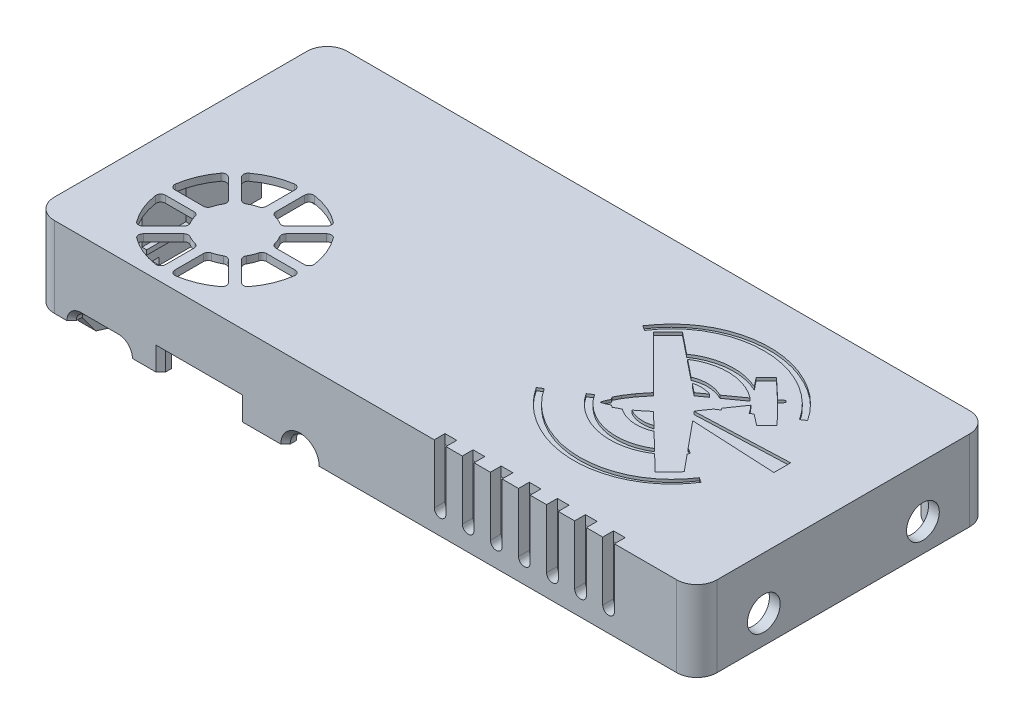
SolidWorks part; units mm, degrees
ref_plane "Front Plane" through (0, 0, 0) normal (0, 0, 1) x (1, 0, 0)
ref_plane "Top Plane" through (0, 0, 0) normal (0, 1, 0) x (1, 0, 0)
ref_plane "Right Plane" through (0, 0, 0) normal (1, 0, 0) x (0, 0, -1)
sketch "Sketch1" plane through (0, 0, 0) normal (0, 1, 0) x (1, 0, 0)
  line L0 (-71.5618, 3.106) -> (63.4382, 3.106) construction
  line L1 (-71.5618, 31.106) -> (63.4382, 31.106)
  line L2 (-71.5618, 31.106) -> (-71.5618, -24.894)
  line L3 (-71.5618, -24.894) -> (63.4382, -24.894)
  line L4 (63.4382, 31.106) -> (63.4382, -24.894)
  line L5 (-60.6618, -24.894) -> (-60.6618, -31.6828) construction
  line L6 (-68.0618, 27.606) -> (-10.0618, 27.606)
  line L7 (-68.0618, 27.606) -> (-68.0618, -21.394)
  line L8 (-68.0618, -21.394) -> (-10.0618, -21.394)
  line L9 (-10.0618, 27.606) -> (-10.0618, -21.394)
  line L10 (-39.5618, -24.894) -> (-39.5618, -31.6828) construction
  line L11 (-18.0618, -24.894) -> (-18.0618, -31.6828) construction
  line L12 (-65.4118, -26.5648) -> (-55.9118, -26.5648) construction
  line L13 (-48.0618, -26.5648) -> (-31.0618, -26.5648) construction
  line L14 (-22.0618, -26.5648) -> (-14.0618, -26.5648) construction
  line L15 (-72.5618, 9.606) -> (-72.5618, -3.394) construction
  line L16 (-71.5618, 3.106) -> (-72.5618, 3.106) construction
  line L17 (-60.6618, -24.894) -> (-60.6618, 40.2849) construction
  dimension "D1" = 135
  dimension "D2" = 56
  dimension "D3" = 49
  dimension "D4" = 58
  dimension "D5" = 3.5
  dimension "D6" = 3.5
  dimension "D7" = 10.9
  dimension "D8" = 32
  dimension "D9" = 53.5
  dimension "D10" = 2
  dimension "D11" = 13
  dimension "D12" = 9.5
  dimension "D13" = 17
  dimension "D14" = 8
sketch "Sketch3" plane through (0, 0, 0) normal (0, 1, 0) x (1, 0, 0)
  line L2 (-72.5618, -25.894) -> (64.4382, -25.894) construction
  line L3 (66.7382, -28.194) -> (66.7382, 34.406) construction
  line L4 (66.7382, 34.406) -> (-74.8618, 34.406)
  line L5 (-74.8618, 34.406) -> (-74.8618, -28.194)
  line L6 (-74.8618, -28.194) -> (66.7382, -28.194)
  line L8 (64.4382, 32.106) -> (-72.5618, 32.106)
  line L9 (64.4382, -25.894) -> (64.4382, 32.106)
  line L10 (-72.5618, -25.894) -> (64.4382, -25.894)
  line L11 (-72.5618, 32.106) -> (-72.5618, -25.894)
  line L12 (64.4382, 32.106) -> (-72.5618, 32.106)
  line L13 (64.4382, -25.894) -> (64.4382, 32.106)
  line L14 (-72.5618, -25.894) -> (64.4382, -25.894)
  line L15 (-72.5618, 32.106) -> (-72.5618, -25.894)
  line L16 (-4.0618, 3.106) -> (-4.0618, 34.406) construction
  line L17 (-71.5618, 3.106) -> (63.4382, 3.106) construction
  line L18 (64.4382, -25.894) -> (64.4382, 32.106) construction
  line L20 (-74.8618, 3.106) -> (52.7382, 3.106) construction
  line L22 (-74.8618, -28.194) -> (66.7382, -28.194) construction
  line L23 (66.7382, -28.194) -> (66.7382, 34.406)
  dimension "D1" = 1
  dimension "D2" = 2.3
extrude "Boss-Extrude1" add sketch "Sketch3" along normal blind 17.2
sketch "Sketch5" plane through (0, 0, 0) normal (0, 1, 0) x (1, 0, 0)
  line L1 (-72.5618, 32.106) -> (64.4382, 32.106)
  line L2 (-72.5618, 32.106) -> (-72.5618, -25.894)
  line L3 (-72.5618, -25.894) -> (64.4382, -25.894)
  line L4 (64.4382, 32.106) -> (64.4382, -25.894)
sketch "Sketch11" plane through (0, 0, 28.194) normal (0, 0, 1) x (1, 0, 0)
  line L0 (-74.8618, 17.2) -> (-74.8618, 0) construction
  line L2 (-66.8618, 0) -> (-54.8618, 0)
  line L3 (-66.8618, 0) -> (-66.8618, 2)
  line L4 (-66.8618, 2) -> (-54.8618, 2)
  line L5 (-54.8618, 0) -> (-54.8618, 2)
  line L9 (-47.8118, 4) -> (-31.3118, 4)
  line L10 (-47.8118, 4) -> (-47.8118, 0)
  line L11 (-47.8118, 0) -> (-31.3118, 0)
  line L12 (-31.3118, 4) -> (-31.3118, 0)
  line L14 (-39.5618, 0) -> (-39.528, 10.3) construction
  line L15 (-48.0618, 0) -> (-31.0618, 0) construction
  line L16 (-18.0618, 0) -> (-18.0618, 10.3) construction
  line L17 (-22.0618, 0) -> (-14.0618, 0) construction
  circle A0 centre (-18.0618, 0) radius 3.1
  dimension "D5" = 6.2
  dimension "D1" = 4
  dimension "D2" = 2
  dimension "D3" = 12
  dimension "D4" = 16.5
  dimension "D7" = 8
extrude "Cut-Extrude1" cut sketch "Sketch11" against normal up to next
sketch "Sketch14" plane through (0, 0, 0) normal (0, -1, 0) x (1, 0, 0)
  line L1 (-74.8618, 11.894) -> (-72.5618, 11.894)
  line L2 (-74.8618, 11.894) -> (-74.8618, -18.106)
  line L3 (-74.8618, -18.106) -> (-72.5618, -18.106)
  line L4 (-72.5618, 11.894) -> (-72.5618, -18.106)
  dimension "D1" = 30
extrude "Boss-Extrude6" add sketch "Sketch14" along normal blind 2.8
sketch "Sketch15" plane through (-74.8618, 0, 0) normal (-1, 0, 0) x (0, 0, 1)
  line L0 (11.894, -2.8) -> (-18.106, -2.8) construction
  line L1 (-9.7403, -2.8) -> (3.7597, -2.8)
  line L2 (-9.7403, -2.8) -> (-9.7403, -1.8)
  line L3 (-9.7403, -1.8) -> (3.7597, -1.8)
  line L4 (3.7597, -2.8) -> (3.7597, -1.8)
sketch "Sketch94" plane through (0, -2.8, 0) normal (0, -1, 0) x (1, 0, 0)
  line L0 (-74.8618, -9.7403) -> (-74.8618, 3.7597) construction
  line L1 (-72.5618, 3.7671) -> (-74.8618, 3.7671)
  line L2 (-72.5618, 3.7671) -> (-72.5618, -9.7403)
  line L3 (-72.5618, -9.7403) -> (-74.8618, -9.7403)
  line L4 (-74.8618, 3.7671) -> (-74.8618, -9.7403)
  line L5 (-74.8618, -30.106) -> (-74.8618, -9.7329) construction
extrude "Boss-Extrude11" add sketch "Sketch94" along normal blind 1.5
sketch "Sketch35" plane through (0, 17.2, 0) normal (0, 1, 0) x (1, 0, 0)
  line L1 (-72.5618, 32.106) -> (64.4382, 32.106)
  line L2 (-72.5618, 32.106) -> (-72.5618, -25.894)
  line L3 (-72.5618, -25.894) -> (64.4382, -25.894)
  line L4 (64.4382, 32.106) -> (64.4382, -25.894)
extrude "Boss-Extrude7" add sketch "Sketch35" against normal blind 2
sketch "Sketch36" plane through (0, 17.2, 0) normal (0, 1, 0) x (1, 0, 0)
  line L0 (24.1618, 0.3922) -> (23.0119, -0.3579)
  line L1 (34.6516, 0.4143) -> (35.8046, -0.3309)
  line L2 (24.1474, 7.2037) -> (22.9944, 7.949)
  line L3 (34.6373, 7.2258) -> (35.7871, 7.9759)
  line L4 (45.9489, -6.8877) -> (46.9923, -7.5622)
  line L5 (39.4174, -2.6661) -> (40.5245, -3.3816)
  line L6 (19.409, -2.7082) -> (18.305, -3.4284)
  line L7 (12.8953, -6.9573) -> (11.8548, -7.6361)
  line L8 (12.8501, 14.5058) -> (11.8067, 15.1802)
  line L9 (19.3816, 10.2841) -> (18.2746, 10.9997)
  line L10 (39.3901, 10.3263) -> (40.4941, 11.0465)
  line L11 (45.9037, 14.5754) -> (46.9443, 15.2542)
  line L12 (52.9704, 2.0329) -> (31.2725, 3.1101)
  line L13 (52.9704, 5.6235) -> (31.2725, 4.7515)
  line L14 (52.9704, 2.0329) -> (52.9704, 5.6235)
  line L15 (31.2725, 3.1101) -> (31.2725, 4.7515)
  arc A0 (46.9443, 15.2542) -> (11.8067, 15.1802) centre (29.3995, 3.809) ccw
  arc A1 (45.9037, 14.5754) -> (12.8501, 14.5058) centre (29.3995, 3.809) ccw
  arc A2 (34.6373, 7.2258) -> (24.1474, 7.2037) centre (29.3995, 3.809) ccw
  arc A3 (35.7871, 7.9759) -> (22.9944, 7.949) centre (29.3995, 3.809) ccw
  arc A4 (40.4941, 11.0465) -> (18.2746, 10.9997) centre (29.3995, 3.809) ccw
  arc A5 (39.3901, 10.3263) -> (19.3816, 10.2841) centre (29.3995, 3.809) ccw
  arc A6 (11.8548, -7.6361) -> (46.9923, -7.5622) centre (29.3995, 3.809) ccw
  arc A7 (12.8953, -6.9573) -> (45.9489, -6.8877) centre (29.3995, 3.809) ccw
  arc A8 (18.305, -3.4284) -> (40.5245, -3.3816) centre (29.3995, 3.809) ccw
  arc A9 (19.409, -2.7082) -> (39.4174, -2.6661) centre (29.3995, 3.809) ccw
  arc A10 (23.0119, -0.3579) -> (35.8046, -0.3309) centre (29.3995, 3.809) ccw
  arc A11 (24.1618, 0.3922) -> (34.6516, 0.4143) centre (29.3995, 3.809) ccw
extrude "Cut-Extrude4" cut sketch "Sketch36" against normal blind 0.6
sketch "Sketch37" plane through (0, 17.2, 0) normal (0, 1, 0) x (1, 0, 0)
  line L0 (28.805, 0.4761) -> (40.1826, -10.5566)
  line L1 (40.1826, -10.5566) -> (43.2384, -7.4053)
  line L2 (43.2384, -7.4053) -> (33.0944, 4.8995)
  line L3 (33.0944, 4.8995) -> (38.1664, 12.1985)
  line L4 (38.1664, 12.1985) -> (42.4176, 8.9024)
  line L5 (42.4176, 8.9024) -> (44.5689, 11.121)
  line L6 (44.5689, 11.121) -> (40.5449, 15.2662)
  line L7 (40.5449, 15.2662) -> (41.3442, 16.2971)
  line L8 (41.3442, 16.2971) -> (41.1146, 16.4751)
  line L9 (28.805, 0.4761) -> (26.7077, -1.2529)
  line L10 (26.7077, -1.2529) -> (24.9219, -2.47)
  line L11 (24.9219, -2.47) -> (23.6139, -3.1724)
  line L12 (23.6139, -3.1724) -> (23.1085, -2.8212)
  line L13 (23.1085, -2.8212) -> (22.3443, -3.2316)
  line L14 (22.3443, -3.2316) -> (21.6545, -3.4615)
  line L15 (21.6545, -3.4615) -> (21.4618, -3.4615)
  line L16 (41.1146, 16.4751) -> (21.4618, -3.4615) construction
  line L17 (21.459, -3.2688) -> (21.4618, -3.4615)
  line L18 (21.6791, -2.5758) -> (21.459, -3.2688)
  line L19 (22.0784, -1.8058) -> (21.6791, -2.5758)
  line L20 (21.72, -1.3055) -> (22.0784, -1.8058)
  line L21 (22.4036, 0.0124) -> (21.72, -1.3055)
  line L22 (23.595, 1.8155) -> (22.4036, 0.0124)
  line L23 (25.2938, 3.9374) -> (23.595, 1.8155)
  line L24 (40.9334, 16.7021) -> (41.1146, 16.4751)
  line L25 (39.9141, 15.8881) -> (40.9334, 16.7021)
  line L26 (35.7115, 19.8523) -> (39.9141, 15.8881)
  line L27 (33.524, 17.6694) -> (35.7115, 19.8523)
  line L28 (36.8807, 13.4659) -> (33.524, 17.6694)
  line L29 (29.6552, 8.2897) -> (36.8807, 13.4659)
  line L30 (17.2062, 18.2563) -> (29.6552, 8.2897)
  line L31 (14.099, 15.1556) -> (17.2062, 18.2563)
  line L32 (25.2938, 3.9374) -> (14.099, 15.1556)
extrude "Cut-Extrude5" cut sketch "Sketch37" against normal blind 0.6
sketch "Sketch48" plane through (0, 17.2, 0) normal (0, 1, 0) x (1, 0, 0)
  line L2 (-74.8618, 3.106) -> (-35.5735, 3.106) construction
  line L3 (-74.8618, 34.406) -> (-74.8618, -28.194) construction
  line L4 (66.7382, -28.194) -> (66.7382, 34.406) construction
  circle A2 centre (62.4382, 30.106) radius 4.3
  circle A3 centre (62.4382, -23.894) radius 4.3
  dimension "D1" = 4.3
extrude "Boss-Extrude9" add sketch "Sketch48" against normal up to vertex (17.2 mm away) up to point (-74.8618, 0, -34.406)
sketch "Sketch87" plane through (0, 15.2, 0) normal (0, -1, 0) x (1, 0, 0)
  line L0 (-68.0618, -24.606) -> (-72.5618, -24.606)
  line L1 (-72.5618, -32.106) -> (-72.5618, -18.106) construction
  line L2 (-72.5618, -24.606) -> (-72.5618, -32.106)
  line L3 (-72.5618, -32.106) -> (-65.0618, -32.106)
  line L4 (-13.0618, -27.606) -> (-13.0618, -32.106)
  line L5 (-70.5618, -32.106) -> (9.9382, -32.106) construction
  line L6 (-13.0618, -32.106) -> (-7.0618, -32.106)
  line L7 (-7.0618, -32.106) -> (-7.0618, -27.606)
  line L8 (-13.0618, 21.394) -> (-13.0618, 25.894)
  line L9 (-66.8618, 25.894) -> (-65.1415, 22.0812)
  line L10 (-68.0618, 18.394) -> (-72.5618, 18.394)
  line L11 (-72.5618, 11.894) -> (-72.5618, 25.894) construction
  line L12 (-72.5618, 18.394) -> (-72.5618, 25.894)
  line L13 (-72.5618, 25.894) -> (-66.8618, 25.894)
  line L14 (-65.0618, -27.606) -> (-65.0618, -32.106)
  line L15 (58.6317, -32.106) -> (-72.5618, -32.106) construction
  line L16 (9.9382, 25.894) -> (-54.8618, 25.894) construction
  line L17 (-13.0618, 25.894) -> (-7.0618, 25.894)
  line L18 (-7.0618, 25.894) -> (-7.0618, 21.394)
  arc A0 (-68.0618, 18.394) -> (-65.6141, 23.1287) centre (-68.0618, 21.394) ccw
  arc A1 (-65.0618, -27.606) -> (-68.0618, -24.606) centre (-68.0618, -27.606) ccw
  arc A2 (-13.0618, 21.394) -> (-7.0618, 21.394) centre (-10.0618, 21.394) ccw
  arc A3 (-7.0618, -27.606) -> (-13.0618, -27.606) centre (-10.0618, -27.606) ccw
  line M11 (58.6317, 25.894) -> (-72.5618, 25.894)
  line M12 (-72.5618, 25.894) -> (-72.5618, -32.106)
  line M13 (-72.5618, -32.106) -> (58.6317, -32.106)
extrude "Boss-Extrude10" add sketch "Sketch87" along normal offset from surface (18.3 mm away) 3.1 contours L10 A0 L9 M11 M12 | L8 A2 L18 M11 | L7 A3 L4 M13 | L2 L3 L14 A1 L0 region at (-10.0618, 15.2, -28.6452) region at (-10.0618, 15.2, 22.4332) region at (-69.1529, 15.2, 22.09) up to face at (-26.2368, 0, 27.044) offset beyond the face yes
fillet "Fillet15" radius 4.3 4 edges at (66.7382, 8.6, -34.406) (66.7382, 8.6, 28.194) (-74.8618, 8.6, -34.406) (-74.8618, 8.6, 28.194)
sketch "Sketch68" plane through (66.7382, 0, 0) normal (1, 0, 0) x (0, 0, -1)
  line L0 (-23.894, 6) -> (30.106, 6) construction
  line L1 (-23.894, 17.2) -> (-23.894, 0) construction
  line L2 (30.106, 0) -> (30.106, 17.2) construction
  line L3 (-23.894, 0) -> (30.106, 0) construction
  circle A0 centre (-13.894, 6) radius 3.5
  circle A1 centre (20.106, 6) radius 3.5
  dimension "D1" = 10
  dimension "D2" = 10
  dimension "D3" = 6
extrude "Cut-Extrude19" cut sketch "Sketch68" against normal up to next
sketch "Sketch81" plane through (0, 0, 28.194) normal (0, 0, 1) x (1, 0, 0)
  line L0 (47.876, 4.6038) -> (47.876, 21.6038) construction
  line L1 (46.626, 4.6038) -> (46.626, 21.6038)
  line L2 (49.126, 4.6038) -> (49.126, 21.6038)
  line L3 (41.876, 4.6038) -> (41.876, 21.6038) construction
  line L4 (40.626, 4.6038) -> (40.626, 21.6038)
  line L5 (43.126, 4.6038) -> (43.126, 21.6038)
  line L6 (35.876, 4.6038) -> (35.876, 21.6038) construction
  line L7 (34.626, 4.6038) -> (34.626, 21.6038)
  line L8 (37.126, 4.6038) -> (37.126, 21.6038)
  line L9 (29.876, 4.6038) -> (29.876, 21.6038) construction
  line L10 (28.626, 4.6038) -> (28.626, 21.6038)
  line L11 (31.126, 4.6038) -> (31.126, 21.6038)
  line L12 (23.876, 4.6038) -> (23.876, 21.6038) construction
  line L13 (22.626, 4.6038) -> (22.626, 21.6038)
  line L14 (25.126, 4.6038) -> (25.126, 21.6038)
  line L15 (17.876, 4.6038) -> (17.876, 21.6038) construction
  line L16 (16.626, 4.6038) -> (16.626, 21.6038)
  line L17 (19.126, 4.6038) -> (19.126, 21.6038)
  line L18 (11.876, 4.6038) -> (11.876, 21.6038) construction
  line L19 (10.626, 4.6038) -> (10.626, 21.6038)
  line L20 (13.126, 4.6038) -> (13.126, 21.6038)
  arc A0 (46.626, 4.6038) -> (49.126, 4.6038) centre (47.876, 4.6038) ccw
  arc A1 (49.126, 21.6038) -> (46.626, 21.6038) centre (47.876, 21.6038) ccw
  arc A2 (40.626, 4.6038) -> (43.126, 4.6038) centre (41.876, 4.6038) ccw
  arc A3 (43.126, 21.6038) -> (40.626, 21.6038) centre (41.876, 21.6038) ccw
  arc A4 (34.626, 4.6038) -> (37.126, 4.6038) centre (35.876, 4.6038) ccw
  arc A5 (37.126, 21.6038) -> (34.626, 21.6038) centre (35.876, 21.6038) ccw
  arc A6 (28.626, 4.6038) -> (31.126, 4.6038) centre (29.876, 4.6038) ccw
  arc A7 (31.126, 21.6038) -> (28.626, 21.6038) centre (29.876, 21.6038) ccw
  arc A8 (22.626, 4.6038) -> (25.126, 4.6038) centre (23.876, 4.6038) ccw
  arc A9 (25.126, 21.6038) -> (22.626, 21.6038) centre (23.876, 21.6038) ccw
  arc A10 (16.626, 4.6038) -> (19.126, 4.6038) centre (17.876, 4.6038) ccw
  arc A11 (19.126, 21.6038) -> (16.626, 21.6038) centre (17.876, 21.6038) ccw
  arc A12 (10.626, 4.6038) -> (13.126, 4.6038) centre (11.876, 4.6038) ccw
  arc A13 (13.126, 21.6038) -> (10.626, 21.6038) centre (11.876, 21.6038) ccw
  point P2 (47.876, 13.1038)
  point P11 (41.876, 13.1038)
  point P18 (35.876, 13.1038)
  point P25 (29.876, 13.1038)
  point P32 (23.876, 13.1038)
  point P39 (17.876, 13.1038)
  point P44 (11.876, 13.1038)
  dimension "D1" = 7
extrude "Cut-Extrude20" cut sketch "Sketch81" against normal up to surface (2.3 mm away) up to face at (-38.6618, 3.7917, 25.894)
fillet "Fillet24" radius 2 2 edges at (58.6317, 7.6, 25.894) (58.6317, 7.6, -32.106)
fillet "Fillet25" radius 2 1 edges at (-54.8618, 2, 27.044)
fillet "Fillet26" radius 2 1 edges at (-66.8618, 2, 27.044)
chamfer "Chamfer1" distance 1 angle 45 7 edges at (-18.0618, 3.1, 28.194) (-31.3118, 2, 28.194) (-39.5618, 4, 28.194) (-47.8118, 2, 28.194) (-55.4476, 1.4142, 28.194) (-60.8618, 2, 28.194) (-66.276, 1.4142, 28.194)
fillet "Fillet51" radius 3 2 edges at (-72.5618, -1.55, -32.106) (-72.5618, -1.55, 25.894)
chamfer "Chamfer3" distance 2 angle 56 8 edges at (-68.2118, -3.1, 25.894) (-71.6831, -3.1, 25.0153) (-72.5618, -3.1, 20.644) (-72.5618, -3.1, -26.856) (-71.6831, -3.1, -31.2273) (-67.3118, -3.1, -32.106) (-10.0618, -3.1, 25.894) (-10.0618, -3.1, -32.106) first distance on face at (-69.08, -3.1, 22.2444) first distance on face at (-68.8118, -3.1, -28.356) first distance on face at (-10.0618, -3.1, 22.894) first distance on face at (-10.0618, -3.1, -29.106)
hole_wizard "Ø2.3 (2.3) Diameter Hole2" positions "Sketch91" profile "Sketch90" hole size "Ø2.3" standard "ANSI Metric"
sketch "Sketch91" plane through (0, 0, 0) normal (0, -1, 0) x (-1, 0, 0)
  point P0 (-62.4382, -23.894)
  point P4 (-62.4382, 30.106)
sketch "Sketch90" plane through (62.4382, 0, 23.894) normal (1, 0, 0) x (0, 0, -1)
  line L0 (0, 0) -> (0, 12)
  line L1 (0, 12) -> (1.15, 12)
  line L2 (1.15, 12) -> (1.15, 0)
  line L5 (1.15, 0) -> (0, 0)
  line L10 (0, 12) -> (-1.15, 12) construction
  line L11 (0, -6.35) -> (0, 107.95) construction
  dimension "Hole Dia." = 2.3
  dimension "Hole Depth" = 12
  dimension "Drill Angle" = 180
hole_wizard "Ø2.3 (2.3) Diameter Hole1" positions "Sketch93" profile "Sketch92" hole size "Ø2.3" standard "ANSI Metric"
sketch "Sketch93" plane through (0, -3.1, 0) normal (0, -1, 0) x (-1, 0, 0)
  point P0 (68.0618, -21.394)
  point P4 (68.0618, 27.606)
  point P7 (10.0618, 27.606)
  point P11 (10.0618, -21.394)
sketch "Sketch92" plane through (-68.0618, -3.1, 21.394) normal (1, 0, 0) x (0, 0, -1)
  line L0 (0, 0) -> (0, 13)
  line L1 (0, 13) -> (1.15, 13)
  line L2 (1.15, 13) -> (1.15, 0)
  line L5 (1.15, 0) -> (0, 0)
  line L10 (0, 13) -> (-1.15, 13) construction
  line L11 (0, -6.35) -> (0, 107.95) construction
  dimension "Hole Dia." = 2.3
  dimension "Hole Depth" = 13
  dimension "Drill Angle" = 180
chamfer "Chamfer4" distance 1 angle 45 1 edges at (-74.8618, -4.3, -2.9866)
sketch "Sketch95" plane through (-74.8618, 0, 0) normal (-1, 0, 0) x (0, 0, 1)
  line L0 (-18.606, 14.2331) -> (-18.606, 8.1669) construction
  line L1 (-25.5774, 11.2) -> (-11.6346, 11.2) construction
  line L2 (-24.606, -3.1) -> (-29.106, -3.1) construction
  line L3 (-24.606, -0.1349) -> (-24.606, -3.1) construction
  line L7 (-23.606, 13.2) -> (-13.606, 13.2)
  line L8 (-23.606, 13.2) -> (-23.606, 9.2)
  line L9 (-23.606, 9.2) -> (-13.606, 9.2)
  line L10 (-13.606, 13.2) -> (-13.606, 9.2)
  line L11 (-23.606, 13.2) -> (-13.606, 9.2) construction
  line L12 (-23.606, 9.2) -> (-13.606, 13.2) construction
  point P6 (-18.606, 11.2)
  dimension "D1" = 14.3
  dimension "D2" = 6
  dimension "D3" = 10
  dimension "D4" = 4
extrude "Cut-Extrude21" cut sketch "Sketch95" against normal up to next
fillet "Fillet52" radius 1 4 edges at (-73.7118, 9.2, -23.606) (-73.7118, 9.2, -13.606) (-73.7118, 13.2, -13.606) (-73.7118, 13.2, -23.606)
chamfer "Chamfer5" distance 1 angle 45 8 edges at (-74.8618, 13.2, -18.606) (-74.8618, 12.9071, -23.3131) (-74.8618, 12.9071, -13.8989) (-74.8618, 11.2, -23.606) (-74.8618, 11.2, -13.606) (-74.8618, 9.4929, -23.3131) (-74.8618, 9.4929, -13.8989) (-74.8618, 9.2, -18.606)
sketch "Sketch96" plane through (0, 15.2, 0) normal (0, -1, 0) x (1, 0, 0)
  line L0 (-31.3118, 25.894) -> (-47.8118, 25.894) construction
  line L1 (-64.7549, -4.606) -> (-34.2549, -4.606)
  line L2 (-64.7549, -4.606) -> (-64.7549, 25.894)
  line L3 (-64.7549, 25.894) -> (-34.2549, 25.894)
  line L4 (-34.2549, -4.606) -> (-34.2549, 25.894)
  dimension "D1" = 30.5
  dimension "D2" = 30.5
extrude "Cut-Extrude22" cut sketch "Sketch96" against normal blind 0.5
sketch "Sketch97" plane through (0, 15.7, 0) normal (0, -1, 0) x (1, 0, 0)
  line L1 (-48.5049, 18.39) -> (-48.5049, 24.5004)
  line L2 (-50.5049, 18.39) -> (-50.5049, 24.5004)
  line L5 (-43.3206, 15.4141) -> (-38.9999, 19.7349)
  line L6 (-44.7348, 16.8283) -> (-40.4141, 21.1491)
  line L7 (-41.759, 9.644) -> (-35.6485, 9.644)
  line L8 (-41.759, 11.644) -> (-35.6485, 11.644)
  line L9 (-44.7348, 4.4597) -> (-40.4141, 0.1389)
  line L10 (-43.3206, 5.8739) -> (-38.9999, 1.5532)
  line L11 (-50.5049, 2.898) -> (-50.5049, -3.2124)
  line L12 (-48.5049, 2.898) -> (-48.5049, -3.2124)
  line L13 (-55.6893, 5.8739) -> (-60.01, 1.5532)
  line L14 (-54.275, 4.4597) -> (-58.5958, 0.1389)
  line L15 (-57.2509, 11.644) -> (-63.3613, 11.644)
  line L16 (-57.2509, 9.644) -> (-63.3613, 9.644)
  line L17 (-54.275, 16.8283) -> (-58.5958, 21.1491)
  line L18 (-55.6893, 15.4141) -> (-60.01, 19.7349)
  arc A0 (-61.518, 19.6266) -> (-64.3511, 12.7869) centre (-49.5049, 10.644) ccw
  arc A1 (-55.5349, 14.1991) -> (-56.2826, 12.394) centre (-49.5049, 10.644) ccw
  arc A2 (-56.2826, 8.894) -> (-55.5349, 7.0889) centre (-49.5049, 10.644) ccw
  arc A3 (-64.3511, 8.5011) -> (-61.518, 1.6614) centre (-49.5049, 10.644) ccw
  arc A4 (-58.4875, -1.369) -> (-51.6478, -4.2021) centre (-49.5049, 10.644) ccw
  arc A5 (-53.0601, 4.614) -> (-51.2549, 3.8663) centre (-49.5049, 10.644) ccw
  arc A6 (-47.7549, 3.8663) -> (-45.9498, 4.614) centre (-49.5049, 10.644) ccw
  arc A7 (-47.3621, -4.2021) -> (-40.5223, -1.369) centre (-49.5049, 10.644) ccw
  arc A8 (-37.4919, 1.6614) -> (-34.6588, 8.5011) centre (-49.5049, 10.644) ccw
  arc A9 (-43.4749, 7.0889) -> (-42.7272, 8.894) centre (-49.5049, 10.644) ccw
  arc A10 (-42.7272, 12.394) -> (-43.4749, 14.1991) centre (-49.5049, 10.644) ccw
  arc A11 (-34.6588, 12.7869) -> (-37.4919, 19.6266) centre (-49.5049, 10.644) ccw
  arc A12 (-40.5223, 22.657) -> (-47.3621, 25.4902) centre (-49.5049, 10.644) ccw
  arc A13 (-45.9498, 16.674) -> (-47.7549, 17.4217) centre (-49.5049, 10.644) ccw
  arc A14 (-51.2549, 17.4217) -> (-53.0601, 16.674) centre (-49.5049, 10.644) ccw
  arc A15 (-51.6478, 25.4902) -> (-58.4875, 22.657) centre (-49.5049, 10.644) ccw
  arc A16 (-56.2826, 8.894) -> (-57.2509, 9.644) centre (-57.2509, 8.644) ccw
  arc A17 (-64.3511, 8.5011) -> (-63.3613, 9.644) centre (-63.3613, 8.644) cw
  arc A18 (-61.518, 1.6614) -> (-60.01, 1.5532) centre (-60.7171, 2.2603) ccw
  arc A19 (-55.6893, 5.8739) -> (-55.5349, 7.0889) centre (-56.3964, 6.581) ccw
  arc A20 (-50.5049, 2.898) -> (-51.2549, 3.8663) centre (-51.5049, 2.898) ccw
  arc A21 (-54.275, 4.4597) -> (-53.0601, 4.614) centre (-53.5679, 3.7526) cw
  arc A22 (-58.4875, -1.369) -> (-58.5958, 0.1389) centre (-57.8887, -0.5682) cw
  arc A23 (-51.6478, -4.2021) -> (-50.5049, -3.2124) centre (-51.5049, -3.2124) ccw
  arc A24 (-47.3621, -4.2021) -> (-48.5049, -3.2124) centre (-47.5049, -3.2124) cw
  arc A25 (-40.5223, -1.369) -> (-40.4141, 0.1389) centre (-41.1212, -0.5682) ccw
  arc A26 (-47.7549, 3.8663) -> (-48.5049, 2.898) centre (-47.5049, 2.898) ccw
  arc A27 (-44.7348, 4.4597) -> (-45.9498, 4.614) centre (-45.4419, 3.7526) ccw
  arc A28 (-38.9999, 1.5532) -> (-37.4919, 1.6614) centre (-38.2928, 2.2603) ccw
  arc A29 (-43.3206, 5.8739) -> (-43.4749, 7.0889) centre (-42.6135, 6.581) cw
  arc A30 (-41.759, 9.644) -> (-42.7272, 8.894) centre (-41.759, 8.644) ccw
  arc A31 (-34.6588, 8.5011) -> (-35.6485, 9.644) centre (-35.6485, 8.644) ccw
  arc A32 (-35.6485, 11.644) -> (-34.6588, 12.7869) centre (-35.6485, 12.644) ccw
  arc A33 (-42.7272, 12.394) -> (-41.759, 11.644) centre (-41.759, 12.644) ccw
  arc A34 (-43.4749, 14.1991) -> (-43.3206, 15.4141) centre (-42.6135, 14.707) cw
  arc A35 (-37.4919, 19.6266) -> (-38.9999, 19.7349) centre (-38.2928, 19.0278) ccw
  arc A36 (-40.4141, 21.1491) -> (-40.5223, 22.657) centre (-41.1212, 21.8562) ccw
  arc A37 (-44.7348, 16.8283) -> (-45.9498, 16.674) centre (-45.4419, 17.5354) cw
  arc A38 (-47.7549, 17.4217) -> (-48.5049, 18.39) centre (-47.5049, 18.39) cw
  arc A39 (-48.5049, 24.5004) -> (-47.3621, 25.4902) centre (-47.5049, 24.5004) cw
  arc A40 (-50.5049, 24.5004) -> (-51.6478, 25.4902) centre (-51.5049, 24.5004) ccw
  arc A41 (-51.2549, 17.4217) -> (-50.5049, 18.39) centre (-51.5049, 18.39) ccw
  arc A42 (-53.0601, 16.674) -> (-54.275, 16.8283) centre (-53.5679, 17.5354) cw
  arc A43 (-58.5958, 21.1491) -> (-58.4875, 22.657) centre (-57.8887, 21.8562) cw
  arc A44 (-60.01, 19.7349) -> (-61.518, 19.6266) centre (-60.7171, 19.0278) ccw
  arc A45 (-55.5349, 14.1991) -> (-55.6893, 15.4141) centre (-56.3964, 14.707) ccw
  arc A46 (-57.2509, 11.644) -> (-56.2826, 12.394) centre (-57.2509, 12.644) ccw
  arc A47 (-63.3613, 11.644) -> (-64.3511, 12.7869) centre (-63.3613, 12.644) cw
  point P43 (-49.5049, 10.644)
  point P80 (-48.5049, 17.5722)
  point P83 (-48.5049, 25.6106)
  point P86 (-50.5049, 25.6106)
  point P89 (-50.5049, 17.5722)
  dimension "D1" = 1
  dimension "D3" = 8
extrude "Cut-Extrude23" cut sketch "Sketch97" against normal up to next
sketch "Sketch98" plane through (0, 15.2, 0) normal (0, -1, 0) x (1, 0, 0)
  line L0 (-64.7549, 25.894) -> (-64.7549, -4.606) construction
  line L1 (-64.7549, 15.2653) -> (-66.7549, 15.2653)
  line L2 (-64.7549, 15.2653) -> (-64.7549, 5.8822)
  line L3 (-64.7549, 5.8822) -> (-66.7549, 5.8822)
  line L4 (-66.7549, 15.2653) -> (-66.7549, 5.8822)
  line L5 (-32.2549, 15.3356) -> (-34.2549, 15.3356)
  line L6 (-32.2549, 5.9524) -> (-34.2549, 5.9524)
  line L7 (-32.2549, 15.3356) -> (-32.2549, 5.9524)
  line L8 (-34.2549, 15.3356) -> (-34.2549, 5.9524)
  dimension "D1" = 2
  dimension "D2" = 2
extrude "Boss-Extrude12" add sketch "Sketch98" along normal blind 7.5
sketch "Sketch100" plane through (-64.7549, 0, 0) normal (1, 0, 0) x (0, 0, -1)
  line L0 (-5.8822, 7.7) -> (-5.8822, 15.2) construction
  line L1 (-15.2653, 7.7) -> (-5.8822, 7.7)
  line L2 (-15.2653, 7.7) -> (-15.2653, 8.7)
  line L3 (-15.2653, 8.7) -> (-5.8822, 8.7)
  line L4 (-5.8822, 7.7) -> (-5.8822, 8.7)
  dimension "D1" = 1
extrude "Boss-Extrude13" add sketch "Sketch100" along normal blind 1
sketch "Sketch101" plane through (-34.2549, 0, 0) normal (-1, 0, 0) x (0, 0, 1)
  line L0 (5.9524, 7.7) -> (5.9524, 15.2) construction
  line L1 (15.3356, 7.7) -> (5.9524, 7.7)
  line L2 (15.3356, 7.7) -> (15.3356, 8.7)
  line L3 (15.3356, 8.7) -> (5.9524, 8.7)
  line L4 (5.9524, 7.7) -> (5.9524, 8.7)
  dimension "D1" = 1
extrude "Boss-Extrude14" add sketch "Sketch101" along normal blind 1
